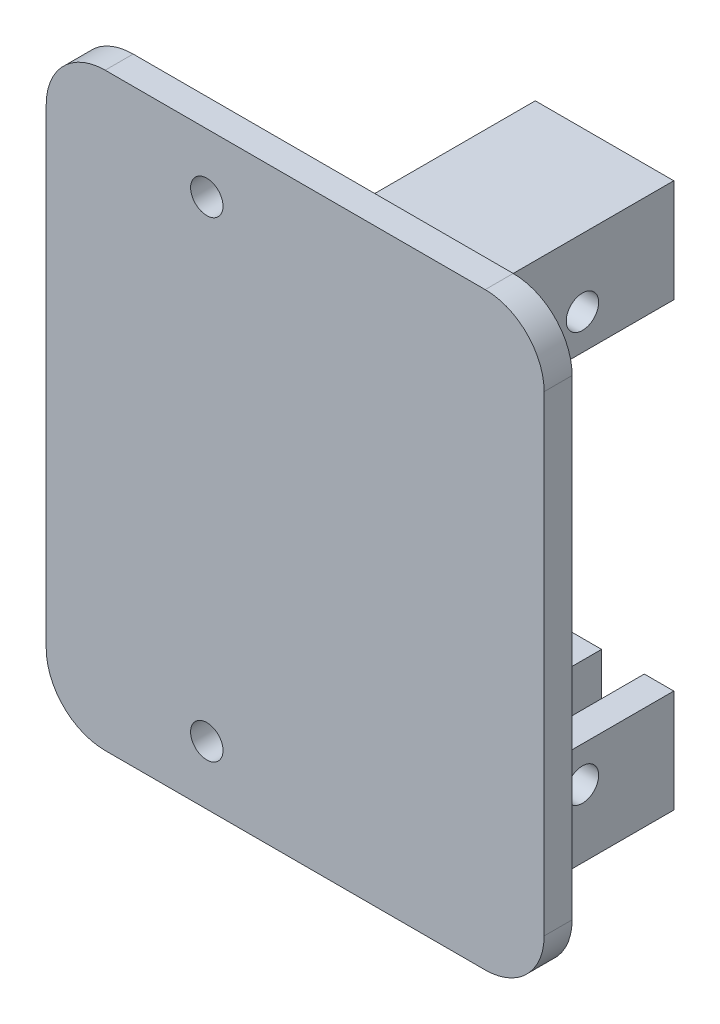
SolidWorks part; units mm, degrees
ref_plane "Płaszczyzna przednia" through (0, 0, 0) normal (0, 0, 1) x (1, 0, 0)
ref_plane "Płaszczyzna górna" through (0, 0, 0) normal (0, 1, 0) x (1, 0, 0)
ref_plane "Płaszczyzna prawa" through (0, 0, 0) normal (1, 0, 0) x (0, 0, -1)
sketch "Szkic1" plane through (0, 0, 0) normal (0, 0, 1) x (1, 0, 0)
  line L0 (-12.9, 20) -> (12.9, 20)
  line L1 (-16.9, 0) -> (16.9, 0) construction
  line L2 (16.9, -16) -> (16.9, 16)
  line L3 (-12.9, -20) -> (12.9, -20)
  line L5 (-16.9, -16) -> (-16.9, 16)
  line L8 (0, 20) -> (0, -20) construction
  arc A0 (12.9, 20) -> (16.9, 16) centre (12.9, 16) cw
  arc A1 (-12.9, -20) -> (-16.9, -16) centre (-12.9, -16) cw
  arc A2 (-12.9, 20) -> (-16.9, 16) centre (-12.9, 16) ccw
  arc A3 (12.9, -20) -> (16.9, -16) centre (12.9, -16) ccw
  point P0 (0, 0)
  point P10 (0, 0)
  dimension "D3" = 4
  dimension "D1" = 20
  dimension "D2" = 16.9
extrude "Dodanie-wyciągnięcie1" add sketch "Szkic1" along normal blind 1.9 contours A1 A0 L5 | L8 A0 region at (0, 0, 0)
sketch "Szkic3" plane through (0, 0, 0) normal (0, 0, -1) x (-1, 0, 0)
  line L11 (-16.9, 0) -> (16.9, 0) construction
  line L12 (-9.4, -16.5) -> (-9.4, -11.5)
  line L13 (-6.5, -16.5) -> (-9.4, -16.5)
  line L39 (-16.9, -16) -> (-16.9, 16) construction
  line L40 (16.9, -16) -> (16.9, 16) construction
  line L41 (-9.4, 11.5) -> (-11.4, 11.5)
  line L42 (-11.4, 11.5) -> (-11.4, 18.5)
  line L43 (-11.4, 18.5) -> (-2, 18.5)
  line L44 (-2, 18.5) -> (-2, 11.5)
  line L45 (-2, 11.5) -> (-6.5, 11.5)
  line L46 (-6.5, 11.5) -> (-6.5, 16.5)
  line L47 (-6.5, 16.5) -> (-9.4, 16.5)
  line L48 (-9.4, 16.5) -> (-9.4, 11.5)
  line L49 (-6.5, -11.5) -> (-6.5, -16.5)
  line L50 (-2, -11.5) -> (-6.5, -11.5)
  line L51 (-2, -18.5) -> (-2, -11.5)
  line L52 (-11.4, -18.5) -> (-2, -18.5)
  line L53 (-11.4, -11.5) -> (-11.4, -18.5)
  line L54 (-9.4, -11.5) -> (-11.4, -11.5)
  point P58 (-10.4, 11.5)
  dimension "D7" = 2
  dimension "D8" = 4.5
  dimension "D9" = 2
  dimension "D10" = 5
  dimension "D11" = 23
  dimension "D12" = 5.5
  dimension "D13" = 2.9
extrude "Dodanie-wyciągnięcie3" add sketch "Szkic3" along normal blind 12.4 contours L48 L47 L46 L45 L44 L43 L42 L41 | L12 L54 L53 L52 L51 L50 L49 L13 region at (6.3467, -15.2827, 0) region at (6.3467, 15.2827, 0)
sketch "Esquisse4" plane through (-16.9, 0, 0) normal (-1, 0, 0) x (0, 0, 1)
  line L0 (-3.5791, 8.3914) -> (0, 5.4422)
  line L1 (0, -16) -> (0, 16) construction
  line L2 (-8.9209, 1.9086) -> (0, -5.4422)
  line L3 (0, 5.4422) -> (0, -5.4422)
  line L14 (1.9, -20) -> (0, -20) construction
  line L15 (1.9, -16) -> (1.9, 16) construction
  circle A3 centre (-6.25, 5.15) radius 2.2
  arc A4 (-3.5791, 8.3914) -> (-8.9209, 1.9086) centre (-6.25, 5.15) ccw
  point P0 (0, 0)
  line M5 (0, 16) -> (0, -16)
  dimension "D5" = 4.4
  dimension "D6" = 2
  dimension "D7" = 25.15
  dimension "D8" = 8.15
extrude "Boss.-Extru.2" add sketch "Esquisse4" against normal blind 2 contours A4 A3 M5 region at (-16.9, 2.8424, -4.2442)
sketch "Esquisse5" plane through (0, 0, 0) normal (0, 0, -1) x (-1, 0, 0)
  line L0 (0, 0) -> (14.9, 0) construction
  line L1 (-2, 18.5) -> (-2, 11.5) construction
  line L8 (14.9, 5.4422) -> (16.9, 5.4422)
  line L9 (16.9, 5.4422) -> (16.9, 16)
  line L10 (12.9, 20) -> (-12.9, 20)
  line L11 (-16.9, 16) -> (-16.9, -16)
  line L12 (-12.9, -20) -> (12.9, -20)
  line L13 (16.9, -16) -> (16.9, -5.4422)
  line L14 (16.9, -5.4422) -> (14.9, -5.4422)
  line L15 (14.9, -5.4422) -> (14.9, 5.4422)
  line L16 (14.9, 5.4422) -> (16.9, 5.4422)
  line L17 (16.9, 5.4422) -> (16.9, 16)
  line L18 (12.9, 20) -> (-12.9, 20)
  line L19 (-16.9, 16) -> (-16.9, -16)
  line L20 (-12.9, -20) -> (12.9, -20)
  line L21 (16.9, -16) -> (16.9, -5.4422)
  line L22 (16.9, -5.4422) -> (14.9, -5.4422)
  line L23 (14.9, -5.4422) -> (14.9, 5.4422)
  circle A0 centre (6, 16) radius 1.1
  circle A1 centre (6, -16) radius 1.1
  arc A4 (16.9, 16) -> (12.9, 20) centre (12.9, 16) ccw
  arc A5 (-12.9, 20) -> (-16.9, 16) centre (-12.9, 16) ccw
  arc A6 (-16.9, -16) -> (-12.9, -20) centre (-12.9, -16) ccw
  arc A7 (12.9, -20) -> (16.9, -16) centre (12.9, -16) ccw
  arc A8 (16.9, 16) -> (12.9, 20) centre (12.9, 16) ccw
  arc A9 (-12.9, 20) -> (-16.9, 16) centre (-12.9, 16) ccw
  arc A10 (-16.9, -16) -> (-12.9, -20) centre (-12.9, -16) ccw
  arc A11 (12.9, -20) -> (16.9, -16) centre (12.9, -16) ccw
  dimension "D3" = 2.2
  dimension "D2" = 4
  dimension "D4" = 8
  dimension "D1" = 0
extrude "Enlèv. mat.-Extru.2" cut sketch "Esquisse5" against normal through all contours A0 | A1 region at (-6, 16, 0) region at (-6, -16, 0)
sketch "Esquisse6" plane through (11.4, 0, 0) normal (1, 0, 0) x (0, 0, -1)
  line L0 (0, 18.5) -> (0, 11.5) construction
  line L1 (0, 11.5) -> (12.4, 11.5) construction
  line L2 (12.4, 11.5) -> (12.4, 18.5) construction
  line L3 (12.4, 18.5) -> (0, 18.5) construction
  line L4 (0, -11.5) -> (0, -18.5) construction
  line L5 (0, -18.5) -> (12.4, -18.5) construction
  line L6 (12.4, -18.5) -> (12.4, -11.5) construction
  line L7 (12.4, -11.5) -> (0, -11.5) construction
  line L8 (0, 18.5) -> (0, 11.5)
  line L9 (0, 11.5) -> (12.4, 11.5)
  line L10 (12.4, 11.5) -> (12.4, 18.5)
  line L11 (12.4, 18.5) -> (0, 18.5)
  line L12 (0, -11.5) -> (0, -18.5)
  line L13 (0, -18.5) -> (12.4, -18.5)
  line L14 (12.4, -18.5) -> (12.4, -11.5)
  line L15 (12.4, -11.5) -> (0, -11.5)
  line L16 (0, 0) -> (-1.9, 0) construction
  line L17 (-1.9, -16) -> (-1.9, 16) construction
  circle A0 centre (6.2, 13.9) radius 1.1
  circle A1 centre (6.2, -13.9) radius 1.1
  point P17 (0, 0)
  point P18 (6.2, 11.5)
  dimension "D1" = 2.2
  dimension "D2" = 27.8
extrude "Enlèv. mat.-Extru.4" cut sketch "Esquisse6" against normal up to surface (9.4 mm away) contours A0 | A1 region at (11.4, 13.9, -6.2) region at (11.4, -13.9, -6.2) up to face at (2, 15, -6.2)
sketch "Esquisse7" plane through (2, 0, 0) normal (-1, 0, 0) x (0, 0, 1)
  circle A0 centre (-6.2, -13.9) radius 1.1 construction
  circle A1 centre (-6.2, 13.9) radius 1.1 construction
  circle A2 centre (-6.2, -13.9) radius 1.1
  circle A3 centre (-6.2, 13.9) radius 1.1
  circle A4 centre (-6.2, 13.9) radius 1.6
  circle A5 centre (-6.2, -13.9) radius 1.6
  dimension "D1" = 3.2
extrude "Enlèv. mat.-Extru.5" cut sketch "Esquisse7" against normal blind 2.2 contours A4 A3 | A3 | A5 A2 | A2 region at (2, -13.9, -6.2) region at (2, 13.9, -6.2) region at (2, 13.9, -7.7547) region at (2, -13.9, -7.7547)
